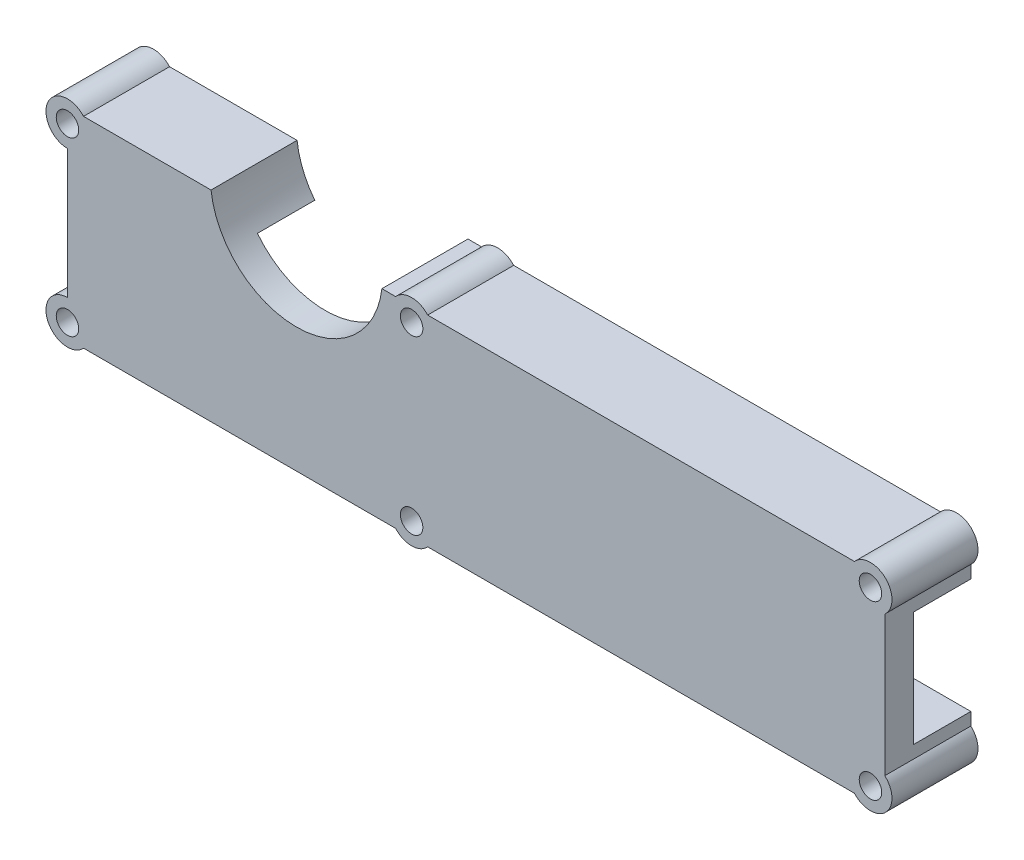
SolidWorks part; units mm, degrees
material "Nylon 101"
ref_plane "Front Plane" through (0, 0, 0) normal (0, 0, 1) x (1, 0, 0)
ref_plane "Top Plane" through (0, 0, 0) normal (0, 1, 0) x (1, 0, 0)
ref_plane "Right Plane" through (0, 0, 0) normal (1, 0, 0) x (0, 0, -1)
sketch "Sketch1" plane through (0, 0, 0) normal (0, 0, 1) x (1, 0, 0)
  line L0 (0, 38.1) -> (101.6, 38.1) construction
  line L1 (3.5498, -3.175) -> (98.0502, -3.175)
  line L3 (3.5498, 41.275) -> (98.0502, 41.275)
  line L4 (104.775, 3.5498) -> (104.775, 34.5502)
  line L5 (101.6, 0) -> (101.6, 38.1) construction
  line L6 (0, 0) -> (101.6, 0) construction
  line L8 (-3.175, 41.275) -> (104.775, 41.275) construction
  line L9 (-3.175, -3.175) -> (-3.175, 41.275) construction
  line L10 (-3.175, -3.175) -> (104.775, -3.175) construction
  line L11 (104.775, -3.175) -> (104.775, 41.275) construction
  line L12 (-3.5498, 41.275) -> (-6.5729, 41.275)
  line L13 (0, 0) -> (-76.2, 0) construction
  line L15 (0, 38.1) -> (-76.2, 38.1) construction
  line L17 (-76.2, 4.7625) -> (-76.2, 33.3375)
  line L18 (-72.6502, -3.175) -> (-3.5498, -3.175)
  line L19 (-44.4127, 41.275) -> (-72.6502, 41.275)
  line L20 (0, 0) -> (0, 38.1) construction
  circle A4 centre (0, 38.1) radius 2.4892
  circle A5 centre (0, 0) radius 2.4892
  circle A6 centre (101.6, 38.1) radius 2.4892
  circle A7 centre (101.6, 0) radius 2.4892
  arc A8 (3.5498, 41.275) -> (-3.5498, 41.275) centre (0, 38.1) ccw
  arc A9 (-3.5498, -3.175) -> (3.5498, -3.175) centre (0, 0) ccw
  circle A10 centre (101.6, 0) radius 4.7625
  circle A11 centre (101.6, 38.1) radius 4.7625
  circle A12 centre (-76.2, 38.1) radius 2.4892
  circle A14 centre (-76.2, 0) radius 2.4892
  arc A15 (-72.6502, 41.275) -> (-76.2, 33.3375) centre (-76.2, 38.1) ccw
  arc A16 (-76.2, 4.7625) -> (-72.6502, -3.175) centre (-76.2, 0) ccw
  arc A17 (-44.4127, 41.275) -> (-6.5729, 41.275) centre (-25.4928, 43.4975) ccw
  point P20 (-35.5701, 19.05)
  dimension "D3" = 4.9784
  dimension "D5" = 9.525
  dimension "D7" = 38.1
  dimension "D1" = 38.1
  dimension "D2" = 101.6
  dimension "D6" = 76.2
  dimension "D8" = 25.4928
  dimension "D9" = 5.3975
  dimension "D4" = 3.175
extrude "Boss-Extrude1" add sketch "Sketch1" along normal blind 19.05 contours L1 L4 L3 A7 A6 A5 A4 | A8 A4 | A9 A5 | A10 A7 | A11 A6 region at (15.12, 18.0645, 0) region at (98.3277, 3.2723, 0) region at (98.3277, 34.8277, 0)
sketch "Sketch2" plane through (-76.2, 0, 0) normal (-1, 0, 0) x (0, 0, 1)
  line L0 (0, 4.7625) -> (0, 33.3375) construction
  line L16 (0, 31.75) -> (0, 6.35)
  line L17 (0, 6.35) -> (12.7, 6.35)
  line L18 (12.7, 6.35) -> (12.7, 31.75)
  line L19 (12.7, 31.75) -> (0, 31.75)
  point P0 (0, 45.5484)
  point P3 (0, 19.05)
  point P9 (0, 19.05)
  dimension "D1" = 12.7
  dimension "D2" = 25.4
extrude "Cut-Extrude1" cut sketch "Sketch2" against normal through all
